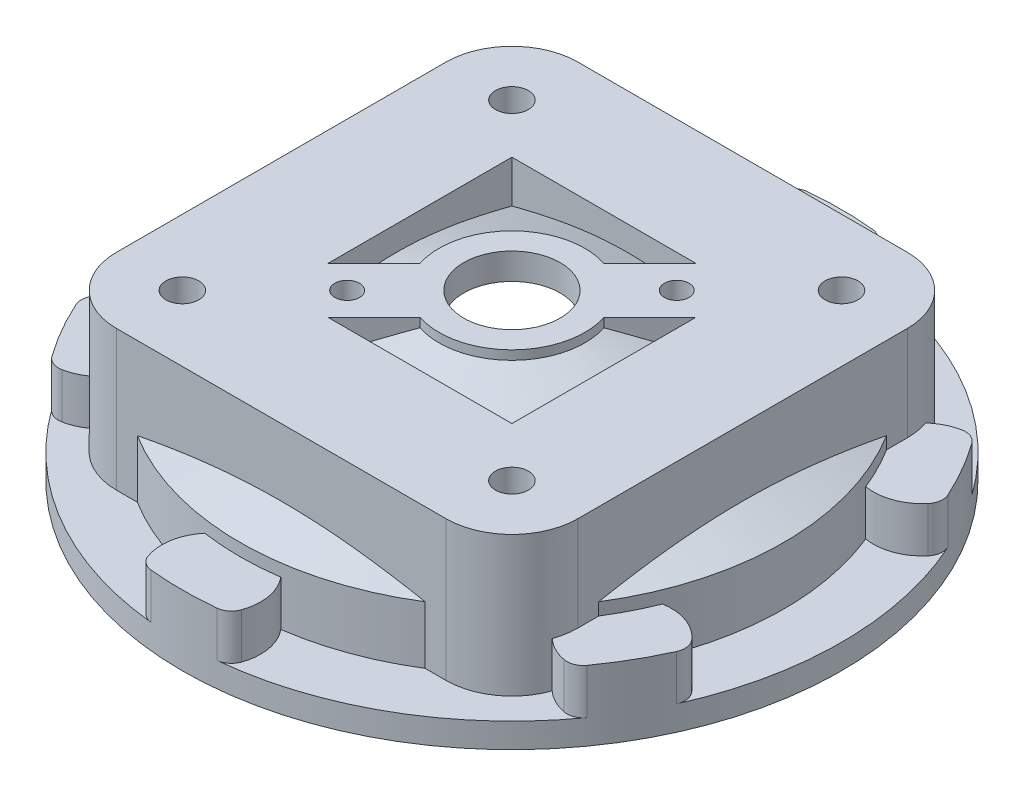
SolidWorks part; units mm, degrees
material "ABS"
ref_plane "Front Plane" through (0, 0, 0) normal (0, 0, 1) x (1, 0, 0)
ref_plane "Top Plane" through (0, 0, 0) normal (0, 1, 0) x (1, 0, 0)
ref_plane "Right Plane" through (0, 0, 0) normal (1, 0, 0) x (0, 0, -1)
sketch "Sketch1" plane through (0, 0, 0) normal (0, 1, 0) x (1, 0, 0)
  circle A0 centre (0, 0) radius 30
  circle A1 centre (0, 0) radius 40
  dimension "D1" = 60
  dimension "D2" = 10
extrude "Boss-Extrude1" add sketch "Sketch1" along normal blind 3
sketch "Sketch2" plane through (0, 3, 0) normal (0, 1, 0) x (1, 0, 0)
  circle A0 centre (0, 0) radius 20 construction
  circle A1 centre (0, 0) radius 30 construction
  circle A2 centre (0, 0) radius 33
  circle A4 centre (0, 0) radius 30
  dimension "D1" = 40
  dimension "D2" = 3
extrude "Boss-Extrude2" add sketch "Sketch2" along normal blind 7
sketch "Sketch3" plane through (0, 0, 0) normal (0, 0, 1) x (1, 0, 0)
  line L0 (-33, 10) -> (-5.8483, 20)
  line L1 (-31.9632, 7.1849) -> (-5.8483, 16.803)
  line L2 (-31.9632, 7.1849) -> (-33, 10)
  line L3 (-5.8483, 16.803) -> (-5.8483, 20)
  line L4 (-33, 10) -> (-6.8851, 19.6181) construction
  line L5 (0, 0) -> (0, 20) construction
  line L6 (0, 20) -> (-5.8483, 20) construction
  dimension "D2" = 20
  dimension "D1" = 3
revolve "Revolve1" add sketch "Sketch3" angle 360 about L5
ref_plane "Plane1" through (0, 20, 0) normal (0, 1, 0) x (1, 0, 0)
sketch "Sketch4" plane through (0, 20, 0) normal (0, 1, 0) x (1, 0, 0)
  line L0 (-28, -20) -> (-28, 20)
  line L1 (-20, -20) -> (20, -20) construction
  line L2 (-20, -20) -> (-20, 20) construction
  line L3 (-20, 20) -> (20, 20) construction
  line L4 (20, -20) -> (20, 20) construction
  line L5 (-20, -20) -> (20, 20) construction
  line L6 (-20, 20) -> (20, -20) construction
  line L7 (-20, 28) -> (20, 28)
  line L8 (28, 20) -> (28, -20)
  line L9 (-20, -28) -> (20, -28)
  line L14 (-14, -8.3431) -> (-8.4093, -2.7525)
  line L15 (-28, -28) -> (28, -28) construction
  line L16 (-28, -28) -> (-28, 28) construction
  line L17 (-28, 28) -> (28, 28) construction
  line L18 (28, -28) -> (28, 28) construction
  line L19 (-28, -28) -> (28, 28) construction
  line L20 (-28, 28) -> (28, -28) construction
  line L21 (14, -14) -> (-8.3431, -14) construction
  line L22 (14, -14) -> (14, 8.3431) construction
  line L23 (8.3431, 14) -> (-14, 14) construction
  line L24 (-14, -8.3431) -> (-14, 14) construction
  line L25 (14, -14) -> (-14, 14) construction
  line L26 (14, 14) -> (-14, -14) construction
  line L27 (10, -10) -> (-10, -10) construction
  line L28 (10, -10) -> (10, 10) construction
  line L29 (10, 10) -> (-10, 10) construction
  line L30 (-10, -10) -> (-10, 10) construction
  line L31 (10, -10) -> (-10, 10) construction
  line L32 (10, 10) -> (-10, -10) construction
  line L33 (14, -14) -> (-8.3431, -14)
  line L34 (14, -14) -> (14, 8.3431)
  line L35 (8.3431, 14) -> (-14, 14)
  line L36 (-14, -8.3431) -> (-14, 14)
  line L37 (14, -14) -> (-14, 14) construction
  line L38 (14, 14) -> (-14, -14) construction
  line L39 (-8.3431, -14) -> (-2.7525, -8.4093)
  line L40 (8.4093, 2.7525) -> (14, 8.3431)
  line L43 (2.7525, 8.4093) -> (8.3431, 14)
  arc A4 (-20, 28) -> (-28, 20) centre (-20, 20) ccw
  arc A5 (28, 20) -> (20, 28) centre (20, 20) ccw
  arc A6 (-28, -20) -> (-20, -28) centre (-20, -20) ccw
  arc A7 (20, -28) -> (28, -20) centre (20, -20) ccw
  circle A8 centre (0, 0) radius 5.8483 construction
  circle A9 centre (0, 0) radius 5.8483
  arc A14 (-2.7525, -8.4093) -> (8.4093, 2.7525) centre (0, 0) ccw
  circle A15 centre (0, 0) radius 8.8483 construction
  arc A16 (2.7525, 8.4093) -> (-8.4093, -2.7525) centre (0, 0) ccw
  point P0 (0, 0)
  dimension "D7" = 56
  dimension "D1" = 40
  dimension "D2" = 40
  dimension "D8" = 56
  dimension "D9" = 56
  dimension "D10" = 14
  dimension "D13" = 20
  dimension "D14" = 3
  dimension "D15" = 4
  dimension "D16" = 4
extrude "Boss-Extrude3" add sketch "Sketch4" against normal up to surface up to face at (0, 10, 33)
sketch "Sketch6" plane through (0, 20, 0) normal (0, 1, 0) x (1, 0, 0)
  line L4 (-20, -28) -> (20, -28)
  line L5 (28, -20) -> (28, 20)
  line L6 (20, 28) -> (-20, 28)
  line L7 (-28, 20) -> (-28, -20)
  line L8 (-20, -28) -> (-17.4642, -28)
  line L9 (28, -20) -> (28, -17.4642)
  line L10 (20, 28) -> (17.4642, 28)
  line L11 (-28, 20) -> (-28, 17.4642)
  line L12 (17.4642, -28) -> (20, -28)
  line L13 (-28, -17.4642) -> (-28, -20)
  line L14 (-17.4642, 28) -> (-20, 28)
  line L15 (28, 17.4642) -> (28, 20)
  arc A4 (-28, -20) -> (-20, -28) centre (-20, -20) ccw
  arc A5 (20, -28) -> (28, -20) centre (20, -20) ccw
  arc A6 (28, 20) -> (20, 28) centre (20, 20) ccw
  arc A7 (-20, 28) -> (-28, 20) centre (-20, 20) ccw
  arc A8 (-28, -20) -> (-20, -28) centre (-20, -20) ccw
  arc A9 (20, -28) -> (28, -20) centre (20, -20) ccw
  arc A10 (28, 20) -> (20, 28) centre (20, 20) ccw
  arc A11 (-20, 28) -> (-28, 20) centre (-20, 20) ccw
  circle A12 centre (0, 0) radius 33 construction
  arc A13 (17.4642, -28) -> (28, -17.4642) centre (0, 0) ccw
  arc A14 (-28, -17.4642) -> (-17.4642, -28) centre (0, 0) ccw
  arc A15 (-17.4642, 28) -> (-28, 17.4642) centre (0, 0) ccw
  arc A16 (28, 17.4642) -> (17.4642, 28) centre (0, 0) ccw
  dimension "D1" = 0
extrude "Boss-Extrude5" add sketch "Sketch6" against normal up to surface (17 mm away) up to face at (0, 3, 40)
sketch "Sketch8" plane through (0, 3, 0) normal (0, 1, 0) x (1, 0, 0)
  line L0 (0, 33) -> (0, 40) construction
  line L1 (0, 36.5) -> (-31.6099, 18.25) construction
  line L2 (-31.6099, 18.25) -> (-31.6099, -18.25) construction
  line L3 (-31.6099, -18.25) -> (0, -36.5) construction
  line L4 (0, -36.5) -> (31.6099, -18.25) construction
  line L5 (31.6099, -18.25) -> (31.6099, 18.25) construction
  line L6 (31.6099, 18.25) -> (0, 36.5) construction
  line L8 (20, -20) -> (-20, -20) construction
  line L9 (20, -20) -> (20, 20) construction
  line L10 (20, 20) -> (-20, 20) construction
  line L11 (-20, -20) -> (-20, 20) construction
  line L12 (20, -20) -> (-20, 20) construction
  line L13 (20, 20) -> (-20, -20) construction
  line L14 (-10, -10) -> (10, -10) construction
  line L15 (-10, -10) -> (-10, 10) construction
  line L16 (-10, 10) -> (10, 10) construction
  line L17 (10, -10) -> (10, 10) construction
  line L18 (-10, -10) -> (10, 10) construction
  line L19 (-10, 10) -> (10, -10) construction
  circle A0 centre (0, 0) radius 31.6099 construction
  arc A1 (17.4642, 28) -> (-17.4642, 28) centre (0, 0) ccw construction
  circle A2 centre (0, 0) radius 40 construction
  point P17 (0, 36.5)
  dimension "D1" = 40
  dimension "D2" = 40
  dimension "D3" = 20
hole_wizard "Ø4.0mm Dowel Hole2" positions "Sketch15" profile "Sketch16" hole size "Ø4.0" standard "ANSI Metric" end condition through all
sketch "Sketch15" plane through (0, 3, 0) normal (0, 1, 0) x (1, 0, 0)
  line L0 (0, 33) -> (0, 40) construction
  point P0 (0, 36.5)
  point P4 (31.6099, 18.25)
  point P7 (31.6099, -18.25)
  point P10 (0, -36.5)
  point P13 (-31.6099, -18.25)
  point P17 (-31.6099, 18.25)
sketch "Sketch16" plane through (0, 3, -36.5) normal (1, 0, 0) x (0, 0, 1)
  line L0 (0, 0) -> (0, 3)
  line L1 (0, 3) -> (2, 3)
  line L2 (2, 3) -> (2, 0)
  line L5 (2, 0) -> (0, 0)
  line L11 (0, -6.35) -> (0, 107.95) construction
  dimension "Thru Hole Dia." = 4
  dimension "Thru Hole Depth" = 3
hole_wizard "Ø4.0mm Dowel Hole3" positions "Sketch17" profile "Sketch18" hole size "Ø4.0" standard "ANSI Metric"
sketch "Sketch17" plane through (0, 20, 0) normal (0, 1, 0) x (1, 0, 0)
  point P0 (-20, 20)
  point P3 (20, 20)
  point P6 (20, -20)
  point P9 (-20, -20)
sketch "Sketch18" plane through (-20, 20, -20) normal (1, 0, 0) x (0, 0, 1)
  line L0 (0, 0) -> (0, 7.7017)
  line L1 (0, 7.7017) -> (2, 6.5)
  line L2 (2, 6.5) -> (2, 0)
  line L5 (2, 0) -> (0, 0)
  line L10 (0, 7.7017) -> (-2, 6.5) construction
  line L11 (0, -6.35) -> (0, 107.95) construction
  dimension "Hole Dia." = 4
  dimension "Hole Depth" = 6.5
  dimension "Drill Angle" = 118
hole_wizard "Ø3.0mm Dowel Hole2" positions "Sketch20" profile "Sketch21" hole size "Ø3.0" standard "ANSI Metric"
sketch "Sketch20" plane through (0, 20, 0) normal (0, 1, 0) x (1, 0, 0)
  point P0 (10, 10)
  point P3 (-10, -10)
sketch "Sketch21" plane through (10, 20, -10) normal (1, 0, 0) x (0, 0, 1)
  line L0 (0, 0) -> (0, 5.1013)
  line L1 (0, 5.1013) -> (1.5, 4.2)
  line L2 (1.5, 4.2) -> (1.5, 0)
  line L5 (1.5, 0) -> (0, 0)
  line L10 (0, 5.1013) -> (-1.5, 4.2) construction
  line L11 (0, -6.35) -> (0, 107.95) construction
  dimension "Hole Dia." = 3
  dimension "Hole Depth" = 4.2
  dimension "Drill Angle" = 118
sketch "Sketch22" plane through (0, 3, 0) normal (0, 1, 0) x (1, 0, 0)
  circle A0 centre (0, 0) radius 40 construction
  arc A1 (-36.9049, -15.4281) -> (-31.8136, -24.2465) centre (0, 0) ccw
  arc A2 (-30.6083, -12.3342) -> (-25.9859, -20.3405) centre (0, 0) ccw
  arc A3 (36.9049, 15.4281) -> (31.8136, 24.2465) centre (0, 0) ccw
  arc A4 (30.6083, 12.3342) -> (25.9859, 20.3405) centre (0, 0) ccw
  arc A5 (30.6083, 12.3342) -> (36.9049, 15.4281) centre (31.6099, 18.25) ccw
  arc A6 (25.9859, -20.3405) -> (30.6083, -12.3342) centre (0, 0) ccw
  arc A7 (31.8136, -24.2465) -> (36.9049, -15.4281) centre (0, 0) ccw
  arc A8 (36.9049, -15.4281) -> (30.6083, -12.3342) centre (31.6099, -18.25) ccw
  arc A9 (-4.6224, -32.6747) -> (4.6224, -32.6747) centre (0, 0) ccw
  arc A10 (-5.0913, -39.6747) -> (5.0913, -39.6747) centre (0, 0) ccw
  arc A11 (5.0913, -39.6747) -> (4.6224, -32.6747) centre (0, -36.5) ccw
  arc A12 (-31.8136, -24.2465) -> (-25.9859, -20.3405) centre (-31.6099, -18.25) ccw
  circle A58 centre (-31.6099, 18.25) radius 6
  arc A59 (-36.9049, 15.4281) -> (-30.6083, 12.3342) centre (-31.6099, 18.25) ccw
  circle A61 centre (0, 36.5) radius 6
  arc A62 (4.6224, 32.6747) -> (5.0913, 39.6747) centre (0, 36.5) ccw
  circle A64 centre (31.6099, 18.25) radius 6
  arc A65 (31.8136, 24.2465) -> (25.9859, 20.3405) centre (31.6099, 18.25) ccw
  circle A67 centre (31.6099, -18.25) radius 6
  arc A68 (25.9859, -20.3405) -> (31.8136, -24.2465) centre (31.6099, -18.25) ccw
  circle A70 centre (0, -36.5) radius 6
  arc A71 (-4.6224, -32.6747) -> (-5.0913, -39.6747) centre (0, -36.5) ccw
  circle A72 centre (-31.6099, -18.25) radius 2 construction
  circle A73 centre (-31.6099, -18.25) radius 6
  arc A74 (-30.6083, -12.3342) -> (-36.9049, -15.4281) centre (-31.6099, -18.25) ccw
  circle A75 centre (0, -36.5) radius 2 construction
  circle A76 centre (31.6099, -18.25) radius 2 construction
  circle A77 centre (31.6099, 18.25) radius 2 construction
  circle A78 centre (0, 36.5) radius 2 construction
  circle A79 centre (-31.6099, 18.25) radius 2 construction
  circle A80 centre (-31.6099, -18.25) radius 2
  circle A81 centre (0, -36.5) radius 2
  circle A82 centre (31.6099, -18.25) radius 2
  circle A83 centre (31.6099, 18.25) radius 2
  circle A84 centre (0, 36.5) radius 2
  circle A85 centre (-31.6099, 18.25) radius 2
  arc A86 (-31.8136, 24.2465) -> (-36.9049, 15.4281) centre (0, 0) ccw
  arc A87 (-25.9859, 20.3405) -> (-30.6083, 12.3342) centre (0, 0) ccw
  arc A88 (-25.9859, 20.3405) -> (-31.8136, 24.2465) centre (-31.6099, 18.25) ccw
  arc A89 (4.6224, 32.6747) -> (-4.6224, 32.6747) centre (0, 0) ccw
  arc A90 (5.0913, 39.6747) -> (-5.0913, 39.6747) centre (0, 0) ccw
  arc A91 (-5.0913, 39.6747) -> (-4.6224, 32.6747) centre (0, 36.5) ccw
  dimension "D1" = 4
  dimension "D2" = 4
  dimension "D3" = 4
  dimension "D4" = 4
  dimension "D5" = 4
  dimension "D6" = 4
extrude "Boss-Extrude7" add sketch "Sketch22" along normal blind 3.5
sketch "Sketch23" plane through (0, 6.5, 0) normal (0, 1, 0) x (1, 0, 0)
  line L0 (-28, -20) -> (-28, -17.4642) construction
  line L1 (28, -17.4642) -> (28, -20) construction
  line L2 (28, 20) -> (28, 17.4642) construction
  line L3 (-28, 17.4642) -> (-28, 20) construction
  line L4 (-28, -20) -> (-28, -17.4642)
  line L5 (28, -17.4642) -> (28, -20)
  line L6 (28, 20) -> (28, 17.4642)
  line L7 (-28, 17.4642) -> (-28, 20)
  arc A0 (-28, -20) -> (-27.544, -22.6623) centre (-20, -20) ccw construction
  arc A1 (-30.6083, -12.3342) -> (-28, -17.4642) centre (0, 0) ccw construction
  arc A2 (-30.6083, -12.3342) -> (-36.9049, -15.4281) centre (-31.6099, -18.25) ccw construction
  arc A3 (-36.9049, -15.4281) -> (-31.8136, -24.2465) centre (0, 0) ccw construction
  arc A4 (-31.8136, -24.2465) -> (-27.544, -22.6623) centre (-31.6099, -18.25) ccw construction
  arc A5 (5.0913, -39.6747) -> (4.6224, -32.6747) centre (0, -36.5) ccw construction
  arc A6 (-4.6224, -32.6747) -> (4.6224, -32.6747) centre (0, 0) ccw construction
  arc A7 (-4.6224, -32.6747) -> (-5.0913, -39.6747) centre (0, -36.5) ccw construction
  arc A8 (-5.0913, -39.6747) -> (5.0913, -39.6747) centre (0, 0) ccw construction
  arc A9 (27.544, -22.6623) -> (28, -20) centre (20, -20) ccw construction
  arc A10 (27.544, -22.6623) -> (31.8136, -24.2465) centre (31.6099, -18.25) ccw construction
  arc A11 (31.8136, -24.2465) -> (36.9049, -15.4281) centre (0, 0) ccw construction
  arc A12 (36.9049, -15.4281) -> (30.6083, -12.3342) centre (31.6099, -18.25) ccw construction
  arc A13 (28, -17.4642) -> (30.6083, -12.3342) centre (0, 0) ccw construction
  arc A14 (28, 20) -> (27.544, 22.6623) centre (20, 20) ccw construction
  arc A15 (30.6083, 12.3342) -> (28, 17.4642) centre (0, 0) ccw construction
  arc A16 (30.6083, 12.3342) -> (36.9049, 15.4281) centre (31.6099, 18.25) ccw construction
  arc A17 (36.9049, 15.4281) -> (31.8136, 24.2465) centre (0, 0) ccw construction
  arc A18 (31.8136, 24.2465) -> (27.544, 22.6623) centre (31.6099, 18.25) ccw construction
  arc A19 (-5.0913, 39.6747) -> (-4.6224, 32.6747) centre (0, 36.5) ccw construction
  arc A20 (4.6224, 32.6747) -> (-4.6224, 32.6747) centre (0, 0) ccw construction
  arc A21 (4.6224, 32.6747) -> (5.0913, 39.6747) centre (0, 36.5) ccw construction
  arc A22 (5.0913, 39.6747) -> (-5.0913, 39.6747) centre (0, 0) ccw construction
  arc A23 (-27.544, 22.6623) -> (-28, 20) centre (-20, 20) ccw construction
  arc A24 (-27.544, 22.6623) -> (-31.8136, 24.2465) centre (-31.6099, 18.25) ccw construction
  arc A25 (-31.8136, 24.2465) -> (-36.9049, 15.4281) centre (0, 0) ccw construction
  arc A26 (-36.9049, 15.4281) -> (-30.6083, 12.3342) centre (-31.6099, 18.25) ccw construction
  arc A27 (-28, 17.4642) -> (-30.6083, 12.3342) centre (0, 0) ccw construction
  arc A28 (-28, -20) -> (-27.544, -22.6623) centre (-20, -20) ccw
  arc A29 (-30.6083, -12.3342) -> (-28, -17.4642) centre (0, 0) ccw
  arc A30 (-30.6083, -12.3342) -> (-36.9049, -15.4281) centre (-31.6099, -18.25) ccw
  arc A31 (-36.9049, -15.4281) -> (-31.8136, -24.2465) centre (0, 0) ccw
  arc A32 (-31.8136, -24.2465) -> (-27.544, -22.6623) centre (-31.6099, -18.25) ccw
  arc A33 (5.0913, -39.6747) -> (4.6224, -32.6747) centre (0, -36.5) ccw
  arc A34 (-4.6224, -32.6747) -> (4.6224, -32.6747) centre (0, 0) ccw
  arc A35 (-4.6224, -32.6747) -> (-5.0913, -39.6747) centre (0, -36.5) ccw
  arc A36 (-5.0913, -39.6747) -> (5.0913, -39.6747) centre (0, 0) ccw
  arc A37 (27.544, -22.6623) -> (28, -20) centre (20, -20) ccw
  arc A38 (27.544, -22.6623) -> (31.8136, -24.2465) centre (31.6099, -18.25) ccw
  arc A39 (31.8136, -24.2465) -> (36.9049, -15.4281) centre (0, 0) ccw
  arc A40 (36.9049, -15.4281) -> (30.6083, -12.3342) centre (31.6099, -18.25) ccw
  arc A41 (28, -17.4642) -> (30.6083, -12.3342) centre (0, 0) ccw
  arc A42 (28, 20) -> (27.544, 22.6623) centre (20, 20) ccw
  arc A43 (30.6083, 12.3342) -> (28, 17.4642) centre (0, 0) ccw
  arc A44 (30.6083, 12.3342) -> (36.9049, 15.4281) centre (31.6099, 18.25) ccw
  arc A45 (36.9049, 15.4281) -> (31.8136, 24.2465) centre (0, 0) ccw
  arc A46 (31.8136, 24.2465) -> (27.544, 22.6623) centre (31.6099, 18.25) ccw
  arc A47 (-5.0913, 39.6747) -> (-4.6224, 32.6747) centre (0, 36.5) ccw
  arc A48 (4.6224, 32.6747) -> (-4.6224, 32.6747) centre (0, 0) ccw
  arc A49 (4.6224, 32.6747) -> (5.0913, 39.6747) centre (0, 36.5) ccw
  arc A50 (5.0913, 39.6747) -> (-5.0913, 39.6747) centre (0, 0) ccw
  arc A51 (-27.544, 22.6623) -> (-28, 20) centre (-20, 20) ccw
  arc A52 (-27.544, 22.6623) -> (-31.8136, 24.2465) centre (-31.6099, 18.25) ccw
  arc A53 (-31.8136, 24.2465) -> (-36.9049, 15.4281) centre (0, 0) ccw
  arc A54 (-36.9049, 15.4281) -> (-30.6083, 12.3342) centre (-31.6099, 18.25) ccw
  arc A55 (-28, 17.4642) -> (-30.6083, 12.3342) centre (0, 0) ccw
extrude "Boss-Extrude8" add sketch "Sketch23" along normal blind 2
fillet "Fillet1" radius 2 12 edges at (-5.0913, 5.75, 39.6747) (-31.8136, 5.75, 24.2465) (-36.9049, 5.75, 15.4281) (-36.9049, 5.75, -15.4281) (-31.8136, 5.75, -24.2465) (-5.0913, 5.75, -39.6747) (5.0913, 5.75, -39.6747) (31.8136, 5.75, -24.2465) (36.9049, 5.75, -15.4281) (36.9049, 5.75, 15.4281) (31.8136, 5.75, 24.2465) (5.0913, 5.75, 39.6747)
